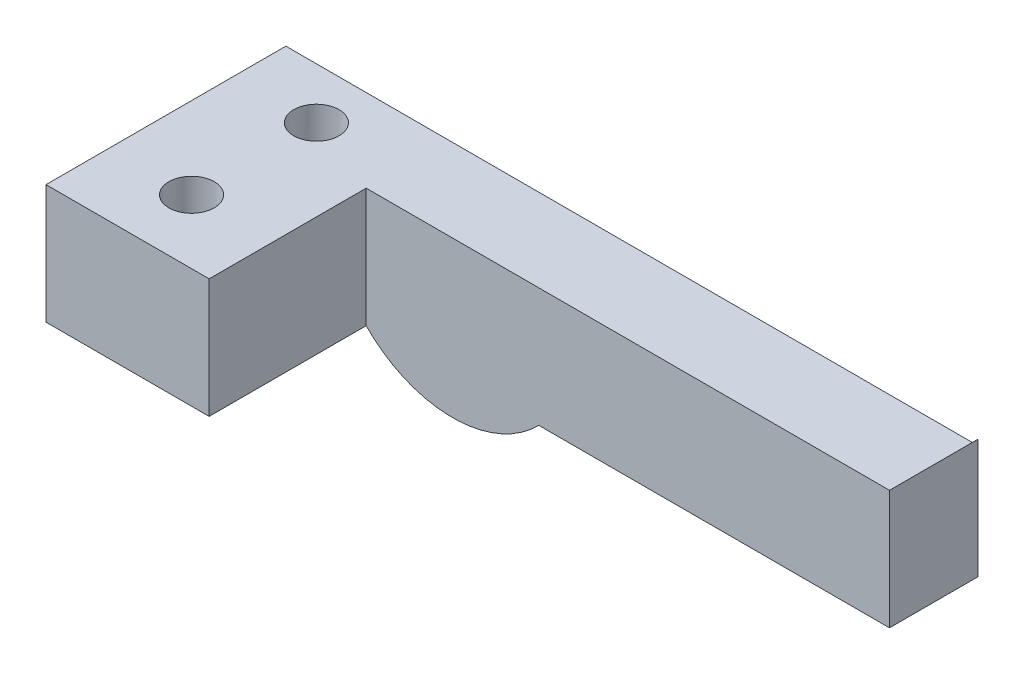
SolidWorks part; units mm, degrees
ref_plane "Front Plane" through (0, 0, 0) normal (0, 0, 1) x (1, 0, 0)
ref_plane "Top Plane" through (0, 0, 0) normal (0, 1, 0) x (1, 0, 0)
ref_plane "Right Plane" through (0, 0, 0) normal (1, 0, 0) x (0, 0, -1)
sketch "Sketch2" plane through (0, 0, 0) normal (0, 0, 1) x (1, 0, 0)
  line L0 (3, 0) -> (31.5, 0)
  line L1 (3, -5.25) -> (1.25, -5.25)
  line L2 (3, -5.25) -> (8.44, -5.25)
  line L3 (31.5, 0) -> (31.5, -5.25)
  line L4 (31.5, -5.25) -> (16.04, -5.25)
  line L5 (8.44, -5.25) -> (8.44, 0)
  line L7 (1.25, -5.25) -> (1.25, 0)
  line L8 (1.25, 0) -> (3, 0)
  arc A0 (8.44, -5.25) -> (16.04, -5.25) centre (12.24, -1.5554) ccw
  dimension "D5" = 5.3
  dimension "D1" = 5.25
  dimension "D2" = 31.5
  dimension "D3" = 28.5
  dimension "D4" = 15.46
  dimension "D6" = 1.75
extrude "Boss-Extrude3" add sketch "Sketch2" along normal blind 10.82 contours L0 L2 L5 region at (4.845, -2.625, 0)
extrude "Boss-Extrude4" add sketch "Sketch2<5>" along normal blind 3.9 contours L5 A0 L4 L3 L0 region at (19.4675, -2.838, 0)
sketch "Sketch2<5>" plane through (0, 0, 0) normal (0, 0, 1) x (1, 0, 0) same geometry as "Sketch2"
sketch "Sketch3" plane through (0, 0, 0) normal (0, 1, 0) x (1, 0, 0)
  line L1 (8.44, -10.82) -> (8.44, -3.9) construction
  line L2 (3, 0) -> (8.44, 0) construction
  circle A0 centre (4.845, -2.5) radius 1
  circle A1 centre (4.845, -8) radius 1
  dimension "D1" = 2
  dimension "D2" = 2
  dimension "D3" = 3.595
  dimension "D4" = 3.595
  dimension "D5" = 2.5
  dimension "D6" = 8
extrude "Cut-Extrude1" cut sketch "Sketch3" against normal up to surface (5.25 mm away) up to face at (5.564, -5.25, 5.108)
sketch "Sketch4" plane through (0, 0, 0) normal (0, 1, 0) x (1, 0, 0)
  line L0 (1.25, 0) -> (1.25, -0.2499)
  line L1 (1.25, -10.82) -> (1.25, 0) construction
  line L2 (1.25, -0.2499) -> (31.4939, -0.2499)
  line L3 (31.4939, -0.2499) -> (31.5, 0)
  line L4 (31.5, 0) -> (1.25, 0)
  dimension "D1" = 0.25
extrude "Cut-Extrude2" cut sketch "Sketch4" against normal blind 10
